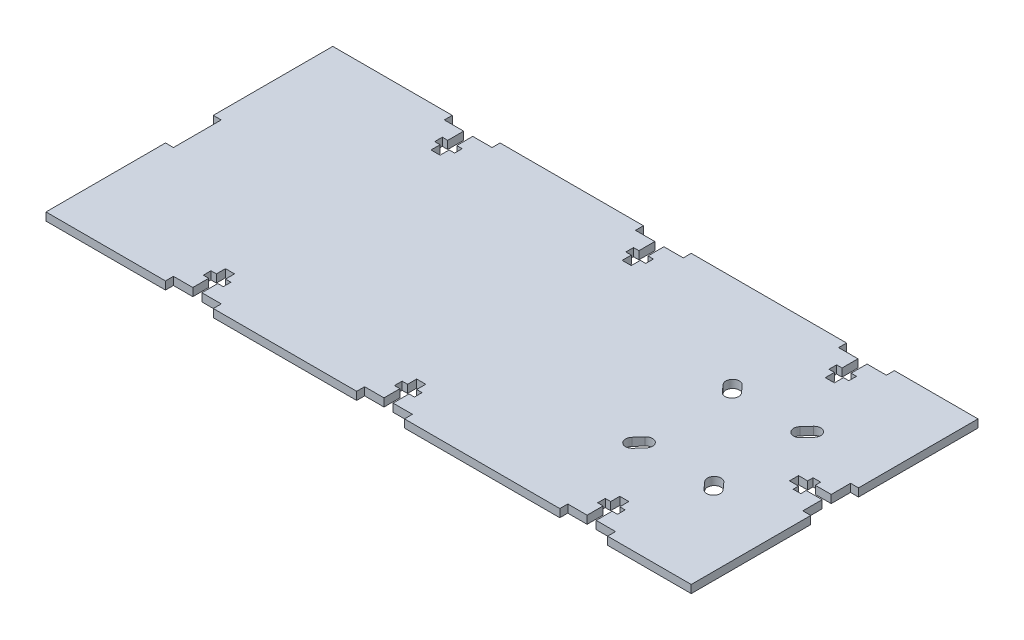
SolidWorks part; units mm, degrees
ref_plane "Front Plane" through (0, 0, 0) normal (0, 0, 1) x (1, 0, 0)
ref_plane "Top Plane" through (0, 0, 0) normal (0, 1, 0) x (1, 0, 0)
ref_plane "Right Plane" through (0, 0, 0) normal (1, 0, 0) x (0, 0, -1)
sketch "Sketch2" plane through (0, 0, 0) normal (0, 1, 0) x (1, 0, 0)
  line L0 (-102.87, -45.72) -> (-64.77, -45.72)
  line L1 (-102.87, 45.72) -> (102.87, 45.72) construction
  line L2 (-102.87, 45.72) -> (-102.87, -45.72) construction
  line L3 (-102.87, -45.72) -> (102.87, -45.72) construction
  line L4 (102.87, 45.72) -> (102.87, -45.72) construction
  line L5 (-102.87, 45.72) -> (102.87, -45.72) construction
  line L6 (-102.87, -45.72) -> (102.87, 45.72) construction
  line L7 (-64.77, -45.72) -> (-64.77, -43.18)
  line L9 (-49.53, -43.18) -> (-49.53, -45.72)
  line L10 (-49.53, -45.72) -> (-3.81, -45.72)
  line L11 (-3.81, -45.72) -> (-3.81, -43.18)
  line L12 (-3.81, -43.18) -> (11.43, -43.18) construction
  line L13 (11.43, -43.18) -> (11.43, -45.72)
  line L14 (11.43, -45.72) -> (60.96, -45.72)
  line L15 (60.96, -45.72) -> (60.96, -43.18)
  line L16 (60.96, -43.18) -> (76.2, -43.18) construction
  line L17 (76.2, -43.18) -> (76.2, -45.72)
  line L18 (76.2, -45.72) -> (102.87, -45.72)
  line L21 (-102.87, 0) -> (102.87, 0) construction
  line L22 (76.2, 43.18) -> (76.2, 45.72)
  line L23 (60.96, 43.18) -> (76.2, 43.18) construction
  line L24 (60.96, 45.72) -> (60.96, 43.18)
  line L25 (11.43, 43.18) -> (11.43, 45.72)
  line L26 (-3.81, 43.18) -> (11.43, 43.18) construction
  line L27 (-3.81, 45.72) -> (-3.81, 43.18)
  line L28 (-49.53, 43.18) -> (-49.53, 45.72)
  line L29 (-64.77, 43.18) -> (-49.53, 43.18) construction
  line L30 (-64.77, 45.72) -> (-64.77, 43.18)
  line L31 (-102.87, 45.72) -> (-64.77, 45.72)
  line L32 (-49.53, 45.72) -> (-3.81, 45.72)
  line L33 (11.43, 45.72) -> (60.96, 45.72)
  line L34 (76.2, 45.72) -> (102.87, 45.72)
  line L35 (-102.87, 45.72) -> (-102.87, 7.62)
  line L36 (-102.87, 7.62) -> (-100.33, 7.62)
  line L37 (-100.33, 7.62) -> (-100.33, -7.62)
  line L38 (-100.33, -7.62) -> (-102.87, -7.62)
  line L39 (-102.87, -7.62) -> (-102.87, -45.72)
  line L40 (0, 45.72) -> (0, -45.72) construction
  line L41 (100.33, -7.62) -> (102.87, -7.62)
  line L42 (102.87, 7.62) -> (100.33, 7.62)
  line L43 (100.33, 7.62) -> (100.33, -7.62) construction
  line L44 (102.87, 45.72) -> (102.87, 7.62)
  line L45 (102.87, -7.62) -> (102.87, -45.72)
  line L46 (-58.5978, -43.18) -> (-58.5978, -38.1)
  line L47 (-58.5978, -38.1) -> (-60.325, -38.1)
  line L48 (-60.325, -38.1) -> (-60.325, -35.668)
  line L49 (-60.325, -35.668) -> (-58.5978, -35.668)
  line L50 (-58.5978, -35.668) -> (-58.5978, -32.766)
  line L51 (-58.5978, -32.766) -> (-55.7022, -32.766)
  line L52 (-64.77, -43.18) -> (-58.5978, -43.18)
  line L53 (-49.53, -43.18) -> (-55.7022, -43.18)
  line L54 (-55.7022, -43.18) -> (-55.7022, -38.1)
  line L55 (-55.7022, -38.1) -> (-53.975, -38.1)
  line L56 (-53.975, -38.1) -> (-53.975, -35.668)
  line L57 (-64.77, -43.18) -> (-49.53, -43.18) construction
  line L58 (-57.15, -43.18) -> (-57.15, -32.766) construction
  line L59 (-53.975, -35.668) -> (-55.7022, -35.668)
  line L60 (-55.7022, -35.668) -> (-55.7022, -32.766)
  line L61 (-3.81, -43.18) -> (2.3622, -43.18)
  line L62 (2.3622, -43.18) -> (2.3622, -38.1)
  line L63 (2.3622, -38.1) -> (0.635, -38.1)
  line L64 (0.635, -38.1) -> (0.635, -35.6679)
  line L65 (0.635, -35.6679) -> (2.3622, -35.6679)
  line L66 (2.3622, -35.6679) -> (2.3622, -32.766)
  line L67 (2.3622, -32.766) -> (5.2578, -32.766)
  line L68 (3.81, -43.18) -> (3.81, -32.766) construction
  line L69 (11.43, -43.18) -> (5.2578, -43.18)
  line L70 (5.2578, -43.18) -> (5.2578, -38.1)
  line L71 (5.2578, -38.1) -> (6.985, -38.1)
  line L72 (6.985, -38.1) -> (6.985, -35.6679)
  line L73 (6.985, -35.6679) -> (5.2578, -35.6679)
  line L74 (5.2578, -35.6679) -> (5.2578, -32.766)
  line L75 (68.58, -43.18) -> (68.58, -32.766) construction
  line L76 (60.96, -43.18) -> (67.1322, -43.18)
  line L77 (67.1322, -43.18) -> (67.1322, -38.1)
  line L78 (67.1322, -38.1) -> (65.405, -38.1)
  line L79 (65.405, -38.1) -> (65.405, -35.6679)
  line L80 (65.405, -35.6679) -> (67.1322, -35.6679)
  line L81 (67.1322, -35.6679) -> (67.1322, -32.766)
  line L82 (67.1322, -32.766) -> (70.0278, -32.766)
  line L83 (70.0278, -35.6679) -> (70.0278, -32.766)
  line L84 (71.755, -35.6679) -> (70.0278, -35.6679)
  line L85 (71.755, -38.1) -> (71.755, -35.6679)
  line L86 (70.0278, -38.1) -> (71.755, -38.1)
  line L87 (76.2, -43.18) -> (70.0278, -43.18)
  line L88 (70.0278, -43.18) -> (70.0278, -38.1)
  line L89 (76.2, 43.18) -> (70.0278, 43.18)
  line L90 (70.0278, 43.18) -> (70.0278, 38.1)
  line L91 (70.0278, 38.1) -> (71.755, 38.1)
  line L92 (71.755, 38.1) -> (71.755, 35.6679)
  line L93 (71.755, 35.6679) -> (70.0278, 35.6679)
  line L94 (70.0278, 35.6679) -> (70.0278, 32.766)
  line L95 (67.1322, 32.766) -> (70.0278, 32.766)
  line L96 (67.1322, 35.6679) -> (67.1322, 32.766)
  line L97 (65.405, 35.6679) -> (67.1322, 35.6679)
  line L98 (65.405, 38.1) -> (65.405, 35.6679)
  line L99 (67.1322, 38.1) -> (65.405, 38.1)
  line L100 (67.1322, 43.18) -> (67.1322, 38.1)
  line L101 (60.96, 43.18) -> (67.1322, 43.18)
  line L102 (11.43, 43.18) -> (5.2578, 43.18)
  line L103 (5.2578, 43.18) -> (5.2578, 38.1)
  line L104 (5.2578, 38.1) -> (6.985, 38.1)
  line L105 (6.985, 38.1) -> (6.985, 35.6679)
  line L106 (6.985, 35.6679) -> (5.2578, 35.6679)
  line L107 (5.2578, 35.6679) -> (5.2578, 32.766)
  line L108 (2.3622, 32.766) -> (5.2578, 32.766)
  line L109 (0.635, 35.6679) -> (2.3622, 35.6679)
  line L110 (2.3622, 38.1) -> (0.635, 38.1)
  line L111 (0.635, 38.1) -> (0.635, 35.6679)
  line L112 (2.3622, 43.18) -> (2.3622, 38.1)
  line L113 (-3.81, 43.18) -> (2.3622, 43.18)
  line L114 (-49.53, 43.18) -> (-55.7022, 43.18)
  line L115 (-55.7022, 43.18) -> (-55.7022, 38.1)
  line L116 (-55.7022, 38.1) -> (-53.975, 38.1)
  line L117 (-53.975, 38.1) -> (-53.975, 35.6679)
  line L118 (-53.975, 35.6679) -> (-55.7022, 35.6679)
  line L119 (-55.7022, 35.6679) -> (-55.7022, 32.766)
  line L120 (-58.5978, 32.766) -> (-55.7022, 32.766)
  line L121 (-58.5978, 35.6679) -> (-58.5978, 32.766)
  line L122 (-60.325, 35.6679) -> (-58.5978, 35.6679)
  line L123 (-60.325, 38.1) -> (-60.325, 35.6679)
  line L124 (-58.5978, 38.1) -> (-60.325, 38.1)
  line L125 (-58.5978, 43.18) -> (-58.5978, 38.1)
  line L126 (-64.77, 43.18) -> (-58.5978, 43.18)
  line L127 (2.3622, 35.6679) -> (2.3622, 32.766)
  line L128 (100.33, -1.4478) -> (95.25, -1.4478)
  line L129 (95.25, -1.4478) -> (95.25, -3.175)
  line L130 (95.25, -3.175) -> (92.8179, -3.175)
  line L131 (92.8179, -3.175) -> (92.8179, -1.4478)
  line L132 (92.8179, -1.4478) -> (89.916, -1.4478)
  line L133 (89.916, -1.4478) -> (89.916, 1.4478)
  line L134 (100.33, -1.4478) -> (100.33, -7.62)
  line L135 (92.8179, 1.4478) -> (89.916, 1.4478)
  line L136 (92.8179, 3.175) -> (92.8179, 1.4478)
  line L137 (95.25, 3.175) -> (92.8179, 3.175)
  line L138 (95.25, 1.4478) -> (95.25, 3.175)
  line L139 (100.33, 1.4478) -> (95.25, 1.4478)
  line L140 (100.33, 1.4478) -> (100.33, 7.62)
  point P0 (0, 0)
  point P128 (89.916, 0)
  dimension "D1" = 205.74
  dimension "D2" = 91.44
  dimension "D3" = 38.1
  dimension "D4" = 15.24
  dimension "D5" = 2.54
  dimension "D6" = 45.72
  dimension "D7" = 49.53
  dimension "D8" = 15.24
  dimension "D9" = 2.54
  dimension "D10" = 12.954
  dimension "D11" = 5.08
  dimension "D12" = 2.432
  dimension "D13" = 6.35
  dimension "D14" = 2.8956
  dimension "D15" = 12.954
  dimension "D16" = 5.08
  dimension "D17" = 2.432
  dimension "D18" = 6.35
  dimension "D19" = 2.8956
  dimension "D20" = 12.954
  dimension "D21" = 5.08
  dimension "D22" = 2.432
  dimension "D23" = 6.35
  dimension "D24" = 2.8956
  dimension "D25" = 12.954
  dimension "D26" = 2.432
  dimension "D27" = 5.08
  dimension "D28" = 2.8956
  dimension "D29" = 6.35
extrude "Boss-Extrude1" add sketch "Sketch2" against normal blind 2.54
sketch "Sketch3" plane through (0, 0, 0) normal (0, 1, 0) x (1, 0, 0)
  line L0 (0, 0) -> (67.31, 0) construction
  line L1 (51.308, 19.05) -> (83.312, 19.05) construction
  line L2 (51.308, 19.05) -> (51.308, -19.05) construction
  line L3 (51.308, -19.05) -> (83.312, -19.05) construction
  line L4 (83.312, 19.05) -> (83.312, -19.05) construction
  line L5 (51.308, 19.05) -> (83.312, -19.05) construction
  line L6 (51.308, -19.05) -> (83.312, 19.05) construction
  line L7 (80.264, 16.002) -> (78.232, 13.7302) construction
  line L8 (81.8732, 14.5627) -> (79.8412, 12.2908)
  line L9 (78.6548, 17.4413) -> (76.6228, 15.1695)
  line L10 (67.31, 0) -> (67.31, 19.05) construction
  line L11 (54.356, 16.002) -> (56.388, 13.7302) construction
  line L12 (52.7468, 14.5627) -> (54.7788, 12.2908)
  line L13 (55.9652, 17.4413) -> (57.9972, 15.1695)
  line L14 (80.264, -16.002) -> (78.232, -13.7302) construction
  line L15 (81.8732, -14.5627) -> (79.8412, -12.2908)
  line L16 (78.6548, -17.4413) -> (76.6228, -15.1695)
  line L17 (54.356, -16.002) -> (56.388, -13.7302) construction
  line L18 (52.7468, -14.5627) -> (54.7788, -12.2908)
  line L19 (55.9652, -17.4413) -> (57.9972, -15.1695)
  arc A0 (81.8732, 14.5627) -> (78.6548, 17.4413) centre (80.264, 16.002) ccw
  arc A1 (76.6228, 15.1695) -> (79.8412, 12.2908) centre (78.232, 13.7302) ccw
  arc A2 (52.7468, 14.5627) -> (55.9652, 17.4413) centre (54.356, 16.002) cw
  arc A3 (57.9972, 15.1695) -> (54.7788, 12.2908) centre (56.388, 13.7302) cw
  arc A4 (81.8732, -14.5627) -> (78.6548, -17.4413) centre (80.264, -16.002) cw
  arc A5 (76.6228, -15.1695) -> (79.8412, -12.2908) centre (78.232, -13.7302) cw
  arc A6 (52.7468, -14.5627) -> (55.9652, -17.4413) centre (54.356, -16.002) ccw
  arc A7 (57.9972, -15.1695) -> (54.7788, -12.2908) centre (56.388, -13.7302) ccw
  point P0 (67.31, 0)
  point P8 (79.248, 14.8661)
  point P15 (82.0462, 17.5431)
  point P17 (78.9462, 13.8526)
  point P18 (80.883, 16.1584)
  point P19 (0, 0)
  point P20 (0, 0)
  point P21 (79.1508, 15.2872)
  point P24 (83.312, 13.9968)
  point P25 (83.312, 14.8308)
  point P26 (55.372, 14.8661)
  point P33 (79.248, -14.8661)
  point P40 (55.372, -14.8661)
  dimension "D4" = 2.159
  dimension "D8" = 5.08
  dimension "D1" = 38.1
  dimension "D2" = 32.004
  dimension "D3" = 67.31
  dimension "D5" = 3.048
  dimension "D6" = 3.048
  dimension "D7" = 3.048
extrude "Cut-Extrude1" cut sketch "Sketch3" against normal up to next
